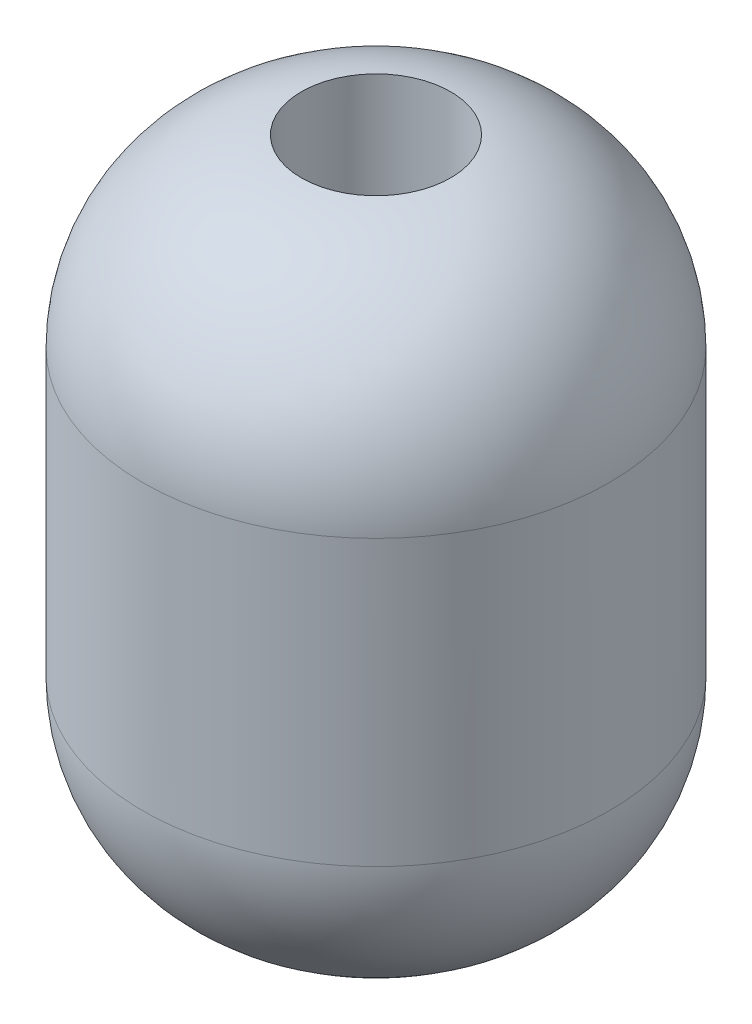
SolidWorks part; units mm, degrees
ref_plane "Plan de face" through (0, 0, 0) normal (0, 0, 1) x (1, 0, 0)
ref_plane "Plan de dessus" through (0, 0, 0) normal (0, 1, 0) x (1, 0, 0)
ref_plane "Plan de droite" through (0, 0, 0) normal (1, 0, 0) x (0, 0, -1)
sketch "Esquisse2" plane through (0, 0, 0) normal (0, 1, 0) x (1, 0, 0)
  circle A0 centre (0, 0) radius 2.5
  circle A1 centre (0, 0) radius 0.8
extrude "Boss.-Extru.1" add sketch "Esquisse2" along normal blind 7
fillet "Congé1" radius 2 2 edges at (0, 0, 2.5) (0, 7, 2.5)
